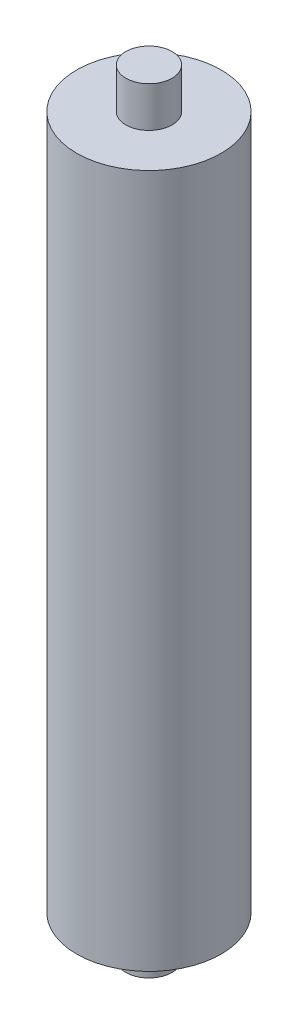
SolidWorks part; units mm, degrees
ref_plane "Plan de face" through (0, 0, 0) normal (0, 0, 1) x (1, 0, 0)
ref_plane "Plan de dessus" through (0, 0, 0) normal (0, 1, 0) x (1, 0, 0)
ref_plane "Plan de droite" through (0, 0, 0) normal (1, 0, 0) x (0, 0, -1)
sketch "Sketch1" plane through (0, 0, 0) normal (0, 1, 0) x (1, 0, 0)
  circle A0 centre (0, 0) radius 12.5
  dimension "D1" = 25
extrude "Boss-Extrude1" add sketch "Sketch1" along normal blind 60 and the other way blind 60
sketch "Sketch2" plane through (0, 60, 0) normal (0, 1, 0) x (1, 0, 0)
  circle A0 centre (0, 0) radius 4
extrude "Boss-Extrude2" add sketch "Sketch2" along normal blind 7
sketch "Sketch3" plane through (0, -60, 0) normal (0, -1, 0) x (1, 0, 0)
  circle A0 centre (0, 0) radius 4
extrude "Boss-Extrude3" add sketch "Sketch3" along normal blind 7
